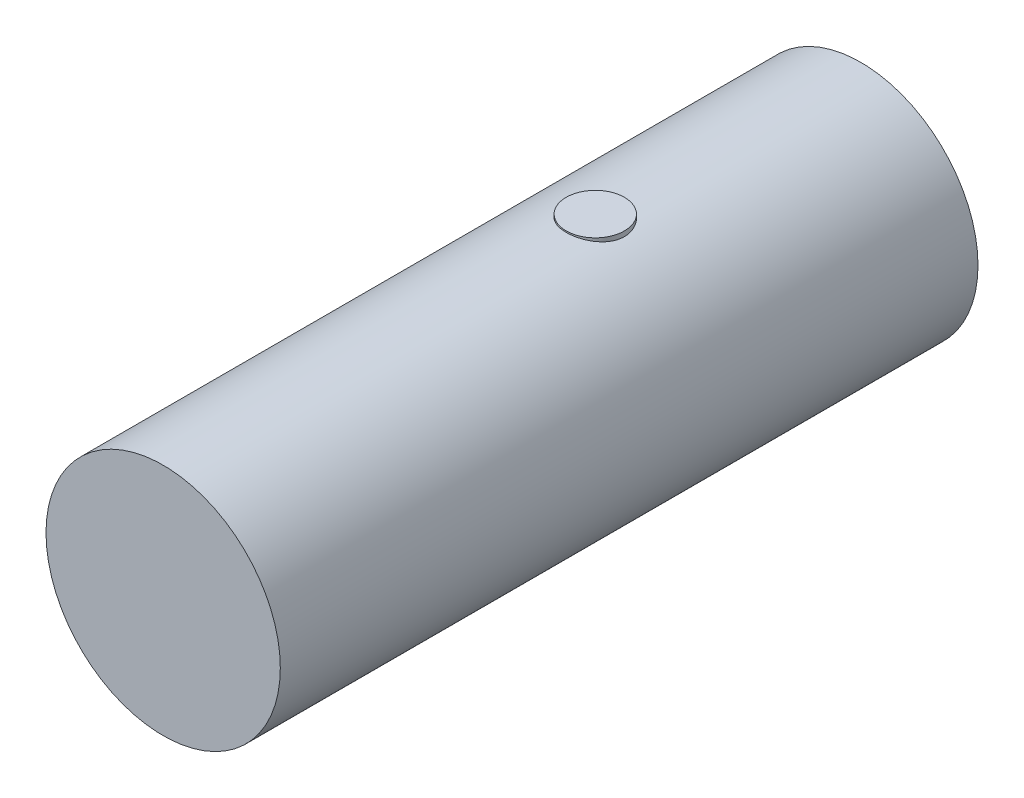
SolidWorks part; units mm, degrees
ref_plane "Ebene vorne" through (0, 0, 0) normal (0, 0, 1) x (1, 0, 0)
ref_plane "Ebene oben" through (0, 0, 0) normal (0, 1, 0) x (1, 0, 0)
ref_plane "Ebene rechts" through (0, 0, 0) normal (1, 0, 0) x (0, 0, -1)
sketch "Skizze1" plane through (0, 0, 0) normal (0, 0, 1) x (1, 0, 0)
  circle A0 centre (0, 0) radius 89
  dimension "D1" = 178
extrude "Aufsatz-Linear austragen1" add sketch "Skizze1" along normal blind 530
sketch "Skizze2" plane through (0, 0, 0) normal (0, 1, 0) x (1, 0, 0)
  line L0 (0, 0) -> (0, -530) construction
  line L1 (-89, -530) -> (89, -530) construction
  circle A0 centre (0, -201.7101) radius 22.1266
extrude "Aufsatz-Linear austragen2" add sketch "Skizze2" along normal blind 90 and the other way blind 90
